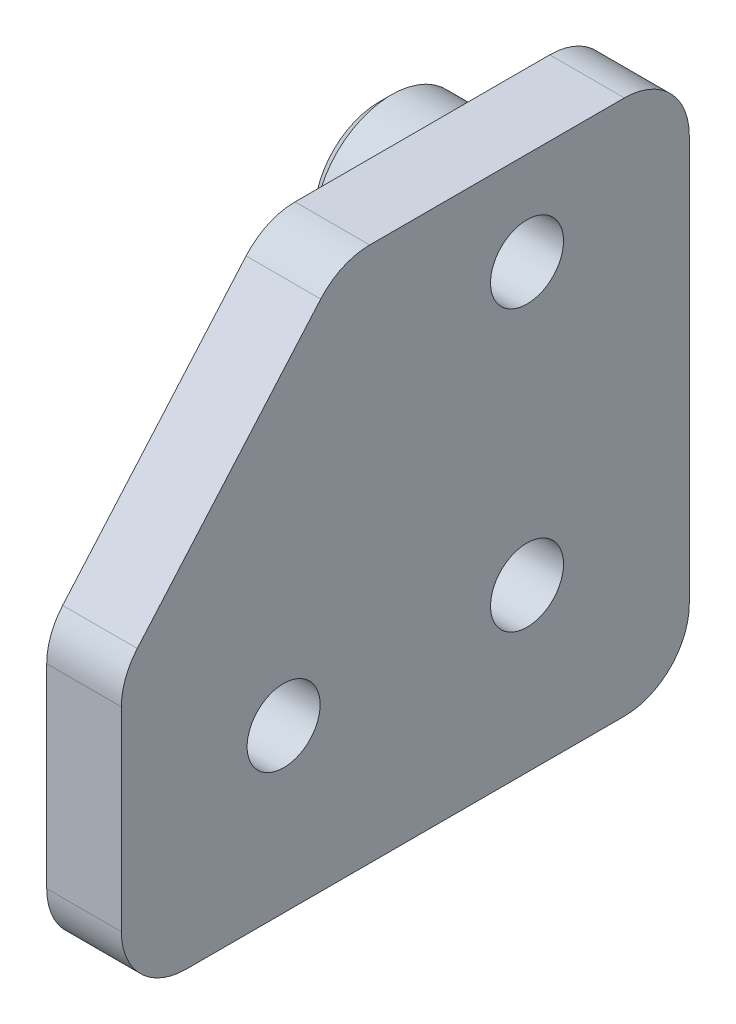
SolidWorks part; units mm, degrees
ref_plane "Front Plane" through (0, 0, 0) normal (0, 0, 1) x (1, 0, 0)
ref_plane "Top Plane" through (0, 0, 0) normal (0, 1, 0) x (1, 0, 0)
ref_plane "Right Plane" through (0, 0, 0) normal (1, 0, 0) x (0, 0, -1)
sketch "Sketch1" plane through (0, 0, 0) normal (1, 0, 0) x (0, 0, -1)
  line L0 (0, -10) -> (0, 23) construction
  line L1 (10, 0) -> (-25, 0) construction
  line L2 (-21, -10) -> (6, -10)
  line L3 (10, -6) -> (10, 19)
  line L4 (6, 23) -> (-9.6957, 23)
  line L5 (-12.7141, 21.6247) -> (-24.0184, 8.6247)
  line L6 (-25, 6) -> (-25, -6)
  line L7 (0, 17.25) -> (-15, 0) construction
  circle A0 centre (0, 0) radius 2 construction
  circle A1 centre (0, 17.25) radius 2 construction
  circle A2 centre (-15, 0) radius 2.25
  circle A3 centre (0, 17.25) radius 2.25
  circle A4 centre (0, 0) radius 2.25
  arc A5 (6, -10) -> (10, -6) centre (6, -6) ccw
  arc A6 (10, 19) -> (6, 23) centre (6, 19) ccw
  arc A7 (-9.6957, 23) -> (-12.7141, 21.6247) centre (-9.6957, 19) ccw
  arc A8 (-24.0184, 8.6247) -> (-25, 6) centre (-21, 6) ccw
  arc A9 (-25, -6) -> (-21, -10) centre (-21, -6) ccw
  point P30 (-25, 0)
  dimension "D2" = 4
  dimension "D3" = 4
  dimension "D10" = 4
  dimension "D5" = 15
  dimension "D6" = 17.25
  dimension "D7" = 10
  dimension "D8" = 10
  dimension "D9" = 5.75
  dimension "D11" = 10
  dimension "D1" = 0.25
  dimension "D4" = 0.25
extrude "Boss-Extrude1" add sketch "Sketch1" along normal blind 4.6
sketch "Sketch2" plane through (0, 0, 0) normal (-1, 0, 0) x (0, 0, 1)
  circle A0 centre (0, 17.25) radius 2.25 construction
  circle A1 centre (0, 17.25) radius 2.25 construction
  circle A2 centre (0, 17.25) radius 2.5
  circle A3 centre (0, 17.25) radius 5 construction
  circle A4 centre (0, 17.25) radius 4.75
  dimension "D1" = 0.25
  dimension "D2" = 10
  dimension "D3" = 0.25
extrude "Boss-Extrude2" add sketch "Sketch2" along normal blind 4.5
chamfer "Chamfer1" distance 0.75 angle 45 1 edges at (-4.5, 17.25, 4.75)
sketch "Sketch3" plane through (4.6, 0, 0) normal (1, 0, 0) x (0, 0, -1)
  line L5 (-21, -10) -> (6, -10)
  line L6 (10, -6) -> (10, 19)
  line L7 (6, 23) -> (-9.6957, 23)
  line L8 (-12.7141, 21.6247) -> (-24.0184, 8.6247)
  line L9 (-25, 6) -> (-25, -6)
  line L10 (-21, -10) -> (6, -10)
  line L11 (10, -6) -> (10, 19)
  line L12 (6, 23) -> (-9.6957, 23)
  line L13 (-12.7141, 21.6247) -> (-24.0184, 8.6247)
  line L14 (-25, 6) -> (-25, -6)
  circle A0 centre (0, 0) radius 4.2174 construction
  circle A1 centre (-15, 0) radius 5.7189
  circle A2 centre (-15, 0) radius 2.25 construction
  circle A3 centre (0, 0) radius 2.25 construction
  arc A5 (-25, -6) -> (-21, -10) centre (-21, -6) ccw
  arc A6 (6, -10) -> (10, -6) centre (6, -6) ccw
  arc A7 (10, 19) -> (6, 23) centre (6, 19) ccw
  arc A8 (-9.6957, 23) -> (-12.7141, 21.6247) centre (-9.6957, 19) ccw
  arc A9 (-24.0184, 8.6247) -> (-25, 6) centre (-21, 6) ccw
  arc A10 (-25, -6) -> (-21, -10) centre (-21, -6) ccw
  arc A11 (6, -10) -> (10, -6) centre (6, -6) ccw
  arc A12 (10, 19) -> (6, 23) centre (6, 19) ccw
  arc A13 (-9.6957, 23) -> (-12.7141, 21.6247) centre (-9.6957, 19) ccw
  arc A14 (-24.0184, 8.6247) -> (-25, 6) centre (-21, 6) ccw
  dimension "D1" = 0
equation "\"Tolerance\"=0.25"
equation "\"D1@Sketch1\"=\"Tolerance\""
equation "\"D4@Sketch1\"=\"Tolerance\""
equation "\"D1@Sketch2\"=\"Tolerance\""
equation "\"D3@Sketch2\"=\"Tolerance\""
